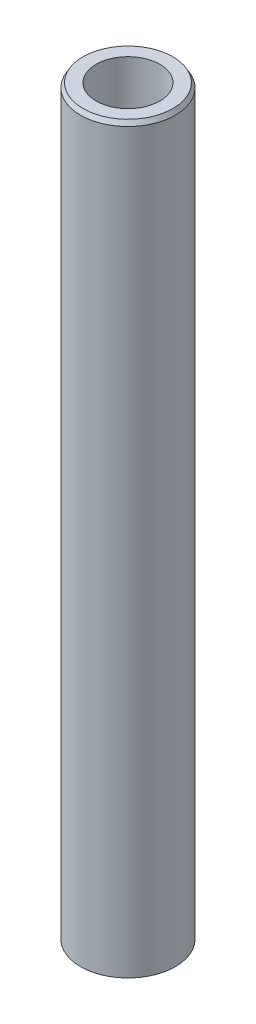
SolidWorks part; units mm, degrees
ref_plane "Front Plane" through (0, 0, 0) normal (0, 0, 1) x (1, 0, 0)
ref_plane "Top Plane" through (0, 0, 0) normal (0, 1, 0) x (1, 0, 0)
ref_plane "Right Plane" through (0, 0, 0) normal (1, 0, 0) x (0, 0, -1)
sketch "Sketch1" plane through (0, 0, 0) normal (0, 1, 0) x (1, 0, 0)
  circle A0 centre (0, 0) radius 12.5
  dimension "SHAFT_OD" = 25
extrude "Boss-Extrude1" add sketch "Sketch1" along normal blind 196.0301
sketch "Sketch2" plane through (0, 0, 0) normal (0, 1, 0) x (1, 0, 0)
  circle A0 centre (0, 0) radius 8.3873
  dimension "BORE_D" = 16.7746
extrude "Cut-Extrude1" cut sketch "Sketch2" along normal through all
chamfer "Chamfer1" distance 1.1753 angle 30 2 edges at (0, 196.0301, 12.5) (0, 0, 12.5) first distance on face at (0, 196.0301, 12.5) first distance on face at (0, 0, 8.3873)
